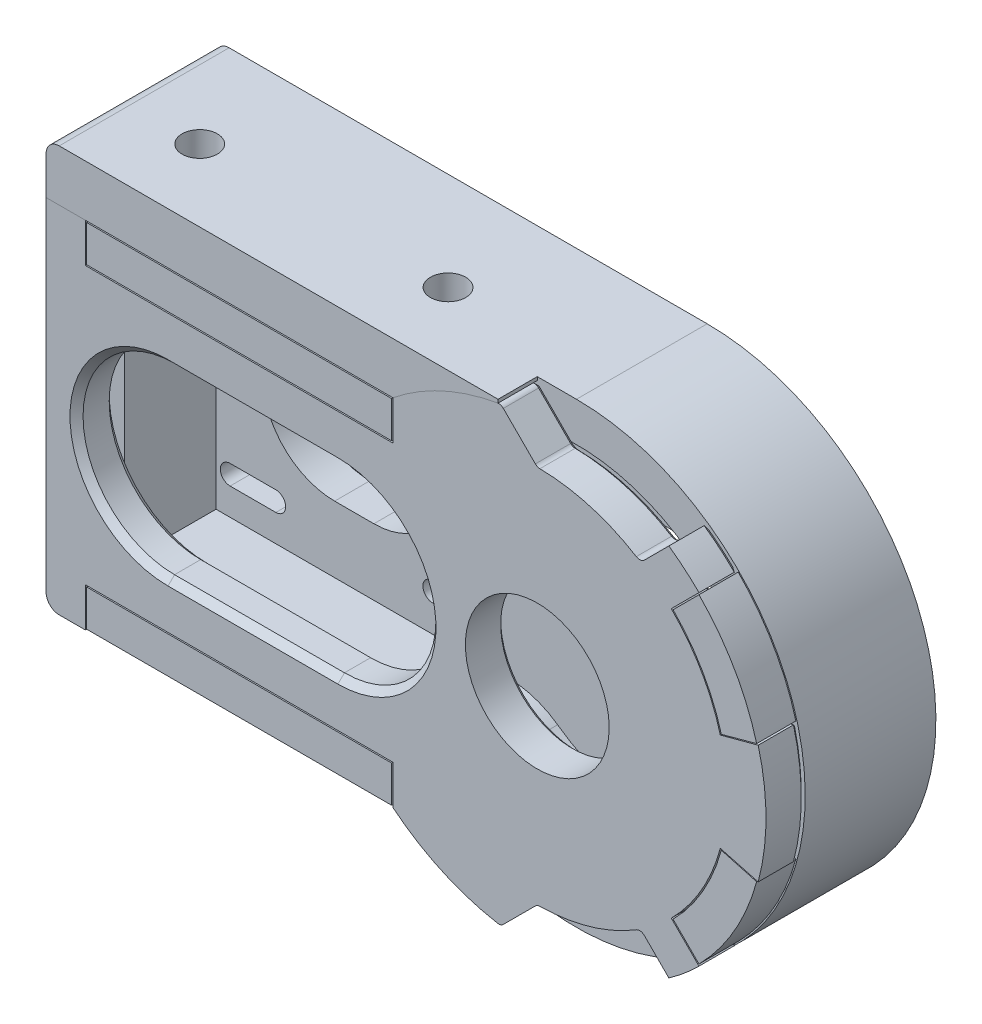
SolidWorks part; units mm, degrees
note: The reader was unsure of these and kept them because the rebuilt part matched: shared geometry of "Sketch3<3>", "Sketch1<3>".
ref_plane "Front Plane" through (0, 0, 0) normal (0, 0, 1) x (1, 0, 0)
ref_plane "Top Plane" through (0, 0, 0) normal (0, 1, 0) x (1, 0, 0)
ref_plane "Right Plane" through (0, 0, 0) normal (1, 0, 0) x (0, 0, -1)
sketch "Sketch1" plane through (0, 0, 0) normal (0, 0, 1) x (1, 0, 0)
  line L0 (21.15, 27.15) -> (-27.15, 27.15)
  line L1 (21.15, -21.15) -> (-21.15, -21.15)
  line L2 (21.15, -21.15) -> (21.15, 21.15)
  line L3 (21.15, 21.15) -> (-21.15, 21.15)
  line L4 (-21.15, -21.15) -> (-21.15, 21.15)
  line L5 (21.15, -21.15) -> (-21.15, 21.15) construction
  line L6 (21.15, 21.15) -> (-21.15, -21.15) construction
  line L7 (21.15, 21.15) -> (71.15, 21.15)
  line L8 (21.15, 21.15) -> (21.15, -21.15)
  line L9 (21.15, -21.15) -> (71.15, -21.15)
  line L10 (71.15, 21.15) -> (71.15, -21.15)
  line L11 (-27.15, -27.15) -> (-27.15, 27.15)
  line L12 (21.15, -27.15) -> (-27.15, -27.15)
  line L13 (21.15, 27.15) -> (28.15, 27.15)
  line L14 (28.15, 27.15) -> (28.15, 21.15)
  line L15 (21.15, -27.15) -> (28.15, -27.15)
  line L16 (28.15, -27.15) -> (28.15, -21.15)
  line L17 (21.15, 33.15) -> (-33.15, 33.15)
  line L18 (-33.15, -33.15) -> (-33.15, 33.15)
  line L19 (21.15, -33.15) -> (-33.15, -33.15)
  circle A0 centre (-15.5, 15.5) radius 1.5
  circle A1 centre (15.5, 15.5) radius 1.5
  circle A2 centre (15.5, -15.5) radius 1.5
  circle A3 centre (-15.5, -15.5) radius 1.5
  circle A4 centre (0, 0) radius 11
  circle A5 centre (0, 0) radius 2.5
  circle A6 centre (48, 0) radius 11
  point P0 (0, 0)
  dimension "D2" = 3
  dimension "D3" = 22
  dimension "D4" = 5
  dimension "D6" = 22
  dimension "D1" = 42.3
  dimension "D5" = 31
  dimension "D7" = 48
  dimension "D8" = 50
  dimension "D10" = 7
  dimension "D9" = 6
  dimension "D11" = 12
extrude "Boss-Extrude1" add sketch "Sketch1" along normal blind 6 contours L4 L1 L2 L3 A4 A3 A2 A1 A0 | L10 L7 L2 L9 A6
sketch "Sketch3" plane through (0, 0, 0) normal (0, 0, 1) x (1, 0, 0)
  line L0 (20.1131, 21.15) -> (28.1587, 21.15)
  line L1 (71.15, 21.15) -> (-21.15, 21.15) construction
  line L2 (20.1131, -21.15) -> (28.1587, -21.15)
  line L3 (71.15, -21.15) -> (-21.15, -21.15) construction
  circle A1 centre (48, 0) radius 29
  circle A2 centre (48, 0) radius 35
  circle A3 centre (48, 0) radius 11
  dimension "D1" = 58
  dimension "D3" = 22
  dimension "D2" = 6
extrude "Boss-Extrude2" add sketch "Sketch3" along normal up to surface (6 mm away) contours A1
extrude "Boss-Extrude3" add sketch "Sketch3<3>" along normal blind 20 contours L2 A2 L0 A1
sketch "Sketch3<3>" plane through (0, 0, 0) normal (0, 0, 1) x (1, 0, 0) same geometry as "Sketch3"
extrude "Boss-Extrude4" add sketch "Sketch1<3>" along normal up to surface (20 mm away) contours L15 L16 L9 L1 L4 L3 L7 L14 L13 L0 L11 L12 up to face at (52.068, 0, 20)
sketch "Sketch1<3>" plane through (0, 0, 0) normal (0, 0, 1) x (1, 0, 0) same geometry as "Sketch1"
sketch "Sketch4" plane through (0, 0, 6) normal (0, 0, 1) x (1, 0, 0)
  line L0 (-19, 15.5) -> (-12, 15.5) construction
  line L1 (-19, 17) -> (-12, 17)
  line L2 (-19, 14) -> (-12, 14)
  line L3 (12, 15.5) -> (19, 15.5) construction
  line L4 (12, 17) -> (19, 17)
  line L5 (12, 14) -> (19, 14)
  line L6 (12, -15.5) -> (19, -15.5) construction
  line L7 (12, -14) -> (19, -14)
  line L8 (12, -17) -> (19, -17)
  line L9 (-12, -15.5) -> (-19, -15.5) construction
  line L10 (-12, -17) -> (-19, -17)
  line L11 (-12, -14) -> (-19, -14)
  line L12 (-3, 0) -> (3, 0) construction
  line L13 (-3, 11) -> (3, 11)
  line L14 (-3, -11) -> (3, -11)
  arc A0 (-19, 17) -> (-19, 14) centre (-19, 15.5) ccw
  arc A1 (-12, 14) -> (-12, 17) centre (-12, 15.5) ccw
  arc A2 (12, 17) -> (12, 14) centre (12, 15.5) ccw
  arc A3 (19, 14) -> (19, 17) centre (19, 15.5) ccw
  arc A4 (12, -14) -> (12, -17) centre (12, -15.5) ccw
  arc A5 (19, -17) -> (19, -14) centre (19, -15.5) ccw
  arc A6 (-12, -17) -> (-12, -14) centre (-12, -15.5) ccw
  arc A7 (-19, -14) -> (-19, -17) centre (-19, -15.5) ccw
  circle A8 centre (-15.5, -15.5) radius 1.5 construction
  circle A9 centre (-15.5, 15.5) radius 1.5 construction
  circle A10 centre (15.5, 15.5) radius 1.5 construction
  circle A11 centre (15.5, -15.5) radius 1.5 construction
  arc A12 (-3, 11) -> (-3, -11) centre (-3, 0) ccw
  arc A13 (3, -11) -> (3, 11) centre (3, 0) ccw
  point P2 (-15.5, 15.5)
  point P7 (15.5, 15.5)
  point P14 (15.5, -15.5)
  point P21 (-15.5, -15.5)
  point P28 (0, 0)
  dimension "D2" = 1.5
  dimension "D4" = 28
  dimension "D1" = 7
  dimension "D3" = 22
extrude "Cut-Extrude1" cut sketch "Sketch4" against normal through all
sketch "Sketch5" plane through (0, 0, 20) normal (0, 0, 1) x (1, 0, 0)
  line L0 (-27.15, -27.15) -> (25.9121, -27.15) construction
  line L1 (-27.15, -27.15) -> (-27.15, 27.15) construction
  line L2 (-27.15, 27.15) -> (25.9121, 27.15) construction
  line L3 (-27.15, -27.15) -> (25.9121, -27.15)
  line L4 (-27.15, -27.15) -> (-27.15, 27.15)
  line L5 (-27.15, 27.15) -> (25.9121, 27.15)
  line L6 (-21.15, -21.15) -> (-21.15, 21.15) construction
  line L7 (28.1587, -21.15) -> (-21.15, -21.15) construction
  line L8 (-21.15, 21.15) -> (28.1587, 21.15) construction
  line L9 (-21.15, -21.15) -> (-21.15, 21.15)
  line L10 (28.1587, -21.15) -> (-21.15, -21.15)
  line L11 (-21.15, 21.15) -> (28.1587, 21.15)
  line L12 (48, 0) -> (72.7487, 24.7487)
  line L13 (-21.15, -21.15) -> (25.9121, -21.15)
  line L14 (-21.15, -21.15) -> (-21.15, -27.15)
  line L15 (-21.15, -27.15) -> (25.9121, -27.15)
  line L16 (25.9121, -21.15) -> (25.9121, -27.15)
  line L17 (-21.15, 21.15) -> (25.9121, 21.15)
  line L18 (-21.15, 21.15) -> (-21.15, 27.15)
  line L19 (-21.15, 27.15) -> (25.9121, 27.15)
  line L20 (25.9121, 21.15) -> (25.9121, 27.15)
  line L21 (48, 0) -> (72.7487, -24.7487)
  line L22 (48, 0) -> (116.9274, 0) construction
  line L23 (39.5147, 0) -> (68.5061, -28.9914)
  line L24 (39.5147, 0) -> (68.5061, 28.9914)
  line L25 (48, 35) -> (48, -35)
  line L26 (48, 0) -> (81.8074, 9.0587)
  line L27 (48, 0) -> (81.8074, -9.0587)
  arc A0 (25.9121, -27.15) -> (25.9121, 27.15) centre (48, 0) ccw construction
  arc A1 (25.9121, -27.15) -> (25.9121, 27.15) centre (48, 0) ccw
  arc A4 (28.1587, -21.15) -> (28.1587, 21.15) centre (48, 0) ccw construction
  arc A5 (28.1587, -21.15) -> (28.1587, 21.15) centre (48, 0) ccw
  circle A7 centre (48, 0) radius 11 construction
  circle A8 centre (48, 0) radius 11
  dimension "D1" = 90
  dimension "D3" = 30
  dimension "D2" = 6
extrude "Boss-Extrude6" add sketch "Sketch5" along normal blind 6 separate body
sketch "Sketch7" plane through (0, 0, 20) normal (0, 0, 1) x (1, 0, 0)
  line L0 (-21.15, 21.15) -> (-21.15, 27.15) construction
  line L1 (-21.15, -21.15) -> (25.9121, -21.15)
  line L2 (-21.15, -21.15) -> (-21.15, -27.15)
  line L3 (-21.15, -27.15) -> (25.9121, -27.15)
  line L4 (25.9121, -21.15) -> (25.9121, -27.15)
  line L5 (-21.15, 27.15) -> (25.9121, 27.15)
  line L6 (-21.15, 27.15) -> (-21.15, 21.15)
  line L7 (-21.15, 21.15) -> (25.9121, 21.15)
  line L8 (25.9121, 27.15) -> (25.9121, 21.15)
  line L9 (-21.15, 21.15) -> (-21.15, 27.15) construction
  line L10 (68.5061, -20.5061) -> (72.7487, -24.7487) construction
  line L11 (68.5061, 20.5061) -> (72.7487, 24.7487) construction
  line L12 (68.5061, -20.5061) -> (72.7487, -24.7487)
  line L13 (68.5061, 20.5061) -> (72.7487, 24.7487)
  line L14 (-20.95, 21.35) -> (25.7121, 21.35)
  line L15 (25.7121, 26.95) -> (25.7121, 21.35)
  line L16 (-20.95, 26.95) -> (25.7121, 26.95)
  line L17 (-20.95, 26.95) -> (-20.95, 21.35)
  line L18 (-20.95, -21.35) -> (25.7121, -21.35)
  line L19 (25.7121, -21.35) -> (25.7121, -26.95)
  line L20 (-20.95, -26.95) -> (25.7121, -26.95)
  line L21 (-20.95, -21.35) -> (-20.95, -26.95)
  line L22 (68.7885, 20.5056) -> (72.7483, 24.4655)
  line L23 (68.7885, -20.5056) -> (72.7483, -24.4655)
  line L24 (-27.15, 27.15) -> (25.9121, 27.15) construction
  arc A0 (28.1587, -21.15) -> (28.1587, 21.15) centre (48, 0) ccw construction
  arc A1 (68.5061, -20.5061) -> (68.5061, 20.5061) centre (48, 0) ccw
  arc A2 (25.9121, -27.15) -> (25.9121, 27.15) centre (48, 0) ccw construction
  arc A3 (72.7487, -24.7487) -> (72.7487, 24.7487) centre (48, 0) ccw
  arc A4 (68.7885, -20.5056) -> (68.7885, 20.5056) centre (48, 0) ccw
  arc A5 (72.7483, -24.4655) -> (72.7483, 24.4655) centre (48, 0) ccw
  dimension "D1" = 0.2
  dimension "D2" = 0.2
sketch "Sketch8" plane through (0, 0, 0) normal (0, 0, -1) x (-1, 0, 0)
  line L0 (-68.7885, 20.5056) -> (-72.7483, 24.4655) construction
  line L1 (-68.7885, -20.5056) -> (-72.7483, -24.4655) construction
  line L2 (20.95, -21.35) -> (-25.7121, -21.35) construction
  line L3 (27.15, 27.15) -> (-25.9121, 27.15)
  line L4 (-25.9121, -27.15) -> (27.15, -27.15)
  line L5 (27.15, -27.15) -> (27.15, 27.15)
  line L6 (27.15, 27.15) -> (-25.9121, 27.15)
  line L7 (-25.9121, -27.15) -> (27.15, -27.15)
  line L8 (27.15, -27.15) -> (27.15, 27.15)
  line L9 (-25.7121, -21.35) -> (-25.7121, -26.95) construction
  line L10 (20.95, -26.95) -> (-25.7121, -26.95) construction
  line L11 (20.95, -21.35) -> (20.95, -26.95) construction
  line L12 (-25.7121, 26.95) -> (-25.7121, 21.35) construction
  line L13 (20.95, 21.35) -> (-25.7121, 21.35) construction
  line L14 (20.95, 26.95) -> (20.95, 21.35) construction
  line L15 (20.95, 26.95) -> (-25.7121, 26.95) construction
  line L16 (-68.7885, 20.5056) -> (-72.7483, 24.4655)
  line L17 (-68.7885, -20.5056) -> (-72.7483, -24.4655)
  line L18 (20.95, -21.35) -> (-25.7121, -21.35)
  line L19 (-25.7121, -21.35) -> (-25.7121, -26.95)
  line L20 (20.95, -26.95) -> (-25.7121, -26.95)
  line L21 (20.95, -21.35) -> (20.95, -26.95)
  line L22 (-25.7121, 26.95) -> (-25.7121, 21.35)
  line L23 (20.95, 21.35) -> (-25.7121, 21.35)
  line L24 (20.95, 26.95) -> (20.95, 21.35)
  line L25 (20.95, 26.95) -> (-25.7121, 26.95)
  line L26 (-48, 0) -> (-81.7676, 9.2061)
  line L27 (-48, 0) -> (-81.7676, -9.2061)
  line L28 (-48, 0) -> (-98.8915, 0) construction
  arc A0 (-68.7885, 20.5056) -> (-68.7885, -20.5056) centre (-48, 0) ccw construction
  arc A1 (-25.9121, 27.15) -> (-25.9121, -27.15) centre (-48, 0) ccw
  arc A2 (-25.9121, 27.15) -> (-25.9121, -27.15) centre (-48, 0) ccw
  arc A3 (-72.7483, 24.4655) -> (-72.7483, -24.4655) centre (-48, 0) ccw construction
  arc A4 (-68.7885, 20.5056) -> (-68.7885, -20.5056) centre (-48, 0) ccw
  arc A5 (-72.7483, 24.4655) -> (-72.7483, -24.4655) centre (-48, 0) ccw
  arc A6 (-25.9121, 27.15) -> (-25.9121, -27.15) centre (-48, 0) ccw construction
  dimension "D2" = 30.5
  dimension "D1" = 0
extrude "Boss-Extrude13" add sketch "Sketch8" against normal up to surface (26 mm away) contours L24 L25 L22 L23 | L21 L18 L19 L20 | L16 A5 L26 A4 | L27 A5 L17 A4 up to face at (39.2775, 0, 26)
sketch "Sketch9" plane through (19.7574, 19.7574, 0) normal (-0.7071, -0.7071, 0) x (0, 0, 1)
  line L0 (26, -68.423) -> (20, -68.423) construction
  line L1 (26, -62.3136) -> (20, -68.423) construction
  line L2 (20, -68.9411) -> (20, 0.8754) construction
  line L3 (20, -62.3136) -> (20, -68.423) construction
  circle A0 centre (23, -65.3683) radius 1.25
  dimension "D1" = 2.5
extrude "Cut-Extrude2" cut sketch "Sketch9" against normal blind 15
mirror "Mirror1" about plane through (0, 0, 0) normal (0, 1, 0) of "Cut-Extrude2"
sketch "Sketch10" plane through (-27.15, 0, 0) normal (-1, 0, 0) x (0, 0, 1)
  line L0 (26, -27.15) -> (20, -27.15) construction
  line L1 (26, 27.15) -> (20, 27.15) construction
  line L2 (26, 27.15) -> (20, 27.15) construction
  circle A0 centre (23, 24.15) radius 1.25
  circle A1 centre (23, -24.15) radius 1.25
  point P10 (23, 27.15)
  dimension "D1" = 2.5
  dimension "D2" = 3
  dimension "D3" = 3
extrude "Cut-Extrude3" cut sketch "Sketch10" against normal blind 15
chamfer "Chamfer2" distance 0.6 angle 45 21 edges at (-20.5, 15.5, 0) (-15.5, 17, 0) (-10.5, 15.5, 0) (-15.5, 14, 0) (-20.5, -15.5, 0) (-15.5, -17, 0) (-10.5, -15.5, 0) (-15.5, -14, 0) (10.5, 15.5, 0) (15.5, 17, 0) (20.5, 15.5, 0) (15.5, 14, 0) (15.5, -17, 0) (20.5, -15.5, 0) (10.5, -15.5, 0) (15.5, -14, 0) (0, 11, 0) (-14, 0, 0) (0, -11, 0) (14, 0, 0) (59, 0, 0)
chamfer "Chamfer3" distance 6 angle 45 2 edges at (48, -35, 23) (48, 35, 23)
fillet "Fillet5" radius 1 6 edges at (63.8198, 24.305, 23) (42.4438, 34.5562, 23) (48, 29, 23) (63.8198, -24.305, 23) (42.4438, -34.5562, 23) (48, -29, 23)
chamfer "Chamfer4" distance 0.6 angle 45 34 edges at (56.0672, 27.8553, 20) (66.2624, 26.7477, 20) (33.4521, 31.8333, 20) (45.2592, 31.7408, 20) (66.2624, -26.7477, 20) (56.0672, -27.8553, 20) (45.2592, -31.7408, 20) (42.4022, -34.4381, 20) (42.4022, 34.4381, 20) (63.7954, 24.5843, 20) (48.028, 29.0759, 20) (63.7954, -24.5843, 20) (48.028, -29.0759, 20) (70.5278, 26.7862, 20) (70.6274, 22.6274, 20) (73.1147, 14.5, 20) (78.9096, 8.2822, 20) (83, 0, 20) (78.9096, -8.2822, 20) (73.1147, -14.5, 20) (70.6274, -22.6274, 20) (70.5278, -26.7862, 20) (33.4521, -31.8333, 20) (25.9121, -24.15, 20) (2.381, -21.15, 20) (-21.15, -24.15, 20) (-24.15, -27.15, 20) (-27.15, 0, 20) (-24.15, 27.15, 20) (-21.15, 24.15, 20) (2.381, 21.15, 20) (25.9121, 24.15, 20) (37, 0, 20) (59, 0, 20)
sketch "Sketch15" plane through (0, 0, 26) normal (0, 0, 1) x (1, 0, 0)
  line L0 (-8.5, 0) -> (17.5, 0) construction
  line L1 (-8.5, 14) -> (17.5, 14)
  line L2 (-8.5, -14) -> (17.5, -14)
  arc A0 (-8.5, 14) -> (-8.5, -14) centre (-8.5, 0) ccw
  arc A1 (17.5, -14) -> (17.5, 14) centre (17.5, 0) ccw
  point P3 (4.5, 0)
  dimension "D2" = 14
  dimension "D1" = 26
  dimension "D3" = 4.5
extrude "Cut-Extrude7" cut sketch "Sketch15" against normal up to next (6 mm away)
fillet "Fillet7" radius 13 2 edges at (28.1587, -21.15, 13) (28.1587, 21.15, 13)
chamfer "Chamfer5" distance 1 angle 45 8 edges at (4.5, -14, 26) (-22.5, 0, 26) (31.5, 0, 26) (4.5, 14, 26) (4.5, -14, 20) (31.5, 0, 20) (-22.5, 0, 20) (4.5, 14, 20)
sketch "Sketch17" plane through (0, 0, 0) normal (0, 0, -1) x (-1, 0, 0)
  line L0 (27.15, 27.15) -> (-25.9121, 27.15) construction
  line L1 (27.15, 27.15) -> (-25.9121, 27.15)
  line L2 (27.15, 27.15) -> (27.15, 35)
  line L3 (27.15, 35) -> (-48, 35)
  arc A0 (-25.9121, 27.15) -> (-25.9121, -27.15) centre (-48, 0) ccw construction
  arc A1 (-25.9121, 27.15) -> (-48, 35) centre (-48, 0) ccw
extrude "Boss-Extrude14" add sketch "Sketch17" against normal up to surface (26 mm away)
sketch "Sketch18" plane through (0, 0, 26) normal (0, 0, 1) x (1, 0, 0)
  line L0 (42, 34.4819) -> (42, 35)
  line L1 (-27.15, 35) -> (48, 35) construction
  line L5 (-27.15, 35) -> (-27.15, 27.15)
  line L6 (-27.15, 27.15) -> (25.9121, 27.15)
  line L7 (48, 35) -> (-27.15, 35)
  line L8 (-27.15, 35) -> (-27.15, 27.15)
  line L9 (-27.15, 27.15) -> (25.9121, 27.15)
  line L10 (48, 35) -> (-27.15, 35)
  arc A1 (48, 35) -> (25.9121, 27.15) centre (48, 0) ccw construction
  arc A2 (48, 35) -> (25.9121, 27.15) centre (48, 0) ccw
  arc A3 (48, 35) -> (25.9121, 27.15) centre (48, 0) ccw
  arc M8 (25.9121, 27.15) -> (48, 35) centre (48, 0) cw
  line M9 (48, 35) -> (-27.15, 35)
  dimension "D2" = 42
  dimension "D1" = 0
extrude "Cut-Extrude8" cut sketch "Sketch18" against normal up to surface (6 mm away) contours L0 M8 M9 up to face at (75.2743, -15.7126, 20)
sketch "Sketch19" plane through (0, 21.15, 0) normal (0, -1, 0) x (1, 0, 0)
  line L0 (-27.15, 20) -> (-27.15, 0) construction
  line L1 (-11.8787, 19.8) -> (-17.4213, 19.8)
  line L2 (-17.4213, 19.8) -> (-20.1926, 15)
  line L3 (-20.1926, 15) -> (-17.4213, 10.2)
  line L4 (-17.4213, 10.2) -> (-11.8787, 10.2)
  line L5 (-11.8787, 10.2) -> (-9.1074, 15)
  line L6 (-9.1074, 15) -> (-11.8787, 19.8)
  line L7 (26.1213, 19.8) -> (20.5787, 19.8)
  line L8 (20.5787, 19.8) -> (17.8074, 15)
  line L9 (17.8074, 15) -> (20.5787, 10.2)
  line L10 (20.5787, 10.2) -> (26.1213, 10.2)
  line L11 (26.1213, 10.2) -> (28.8926, 15)
  line L12 (28.8926, 15) -> (26.1213, 19.8)
  circle A0 centre (-14.65, 15) radius 4.8 construction
  circle A1 centre (23.35, 15) radius 4.8 construction
  dimension "D1" = 9.6
  dimension "D2" = 12.5
  dimension "D3" = 38
  dimension "D4" = 15
extrude "Cut-Extrude9" cut sketch "Sketch19" against normal blind 4.5
sketch "Sketch20" plane through (0, 21.15, 0) normal (0, -1, 0) x (1, 0, 0)
  circle A0 centre (-14.65, 15) radius 2.7
  circle A1 centre (23.35, 15) radius 2.7
  dimension "D2" = 5.4
extrude "Cut-Extrude10" cut sketch "Sketch20" against normal through all
fillet "Fillet8" radius 2 3 edges at (-27.15, 35, 13) (-27.15, -27.15, 10) (25.9121, -27.15, 10)
fillet "Fillet9" radius 2 1 edges at (-27.15, -27.15, 23.3)
